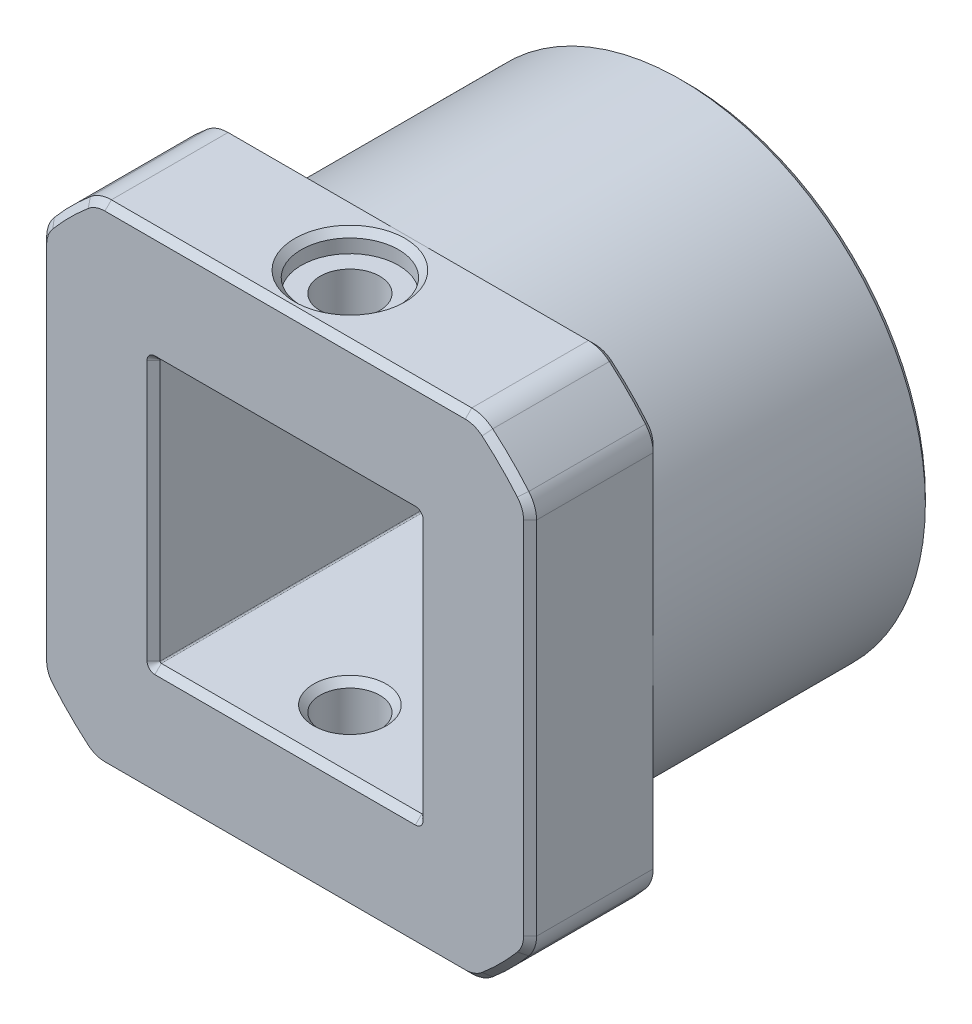
SolidWorks part; units mm, degrees
ref_plane "Front" through (0, 0, 0) normal (0, 0, 1) x (1, 0, 0)
ref_plane "Top" through (0, 0, 0) normal (0, 1, 0) x (1, 0, 0)
ref_plane "Right" through (0, 0, 0) normal (1, 0, 0) x (0, 0, -1)
sketch "Skizze1" plane through (0, 0, 0) normal (0, 0, 1) x (1, 0, 0)
  line L1 (-10.15, -10.15) -> (10.15, -10.15)
  line L2 (-10.15, -10.15) -> (-10.15, 10.15)
  line L3 (-10.15, 10.15) -> (10.15, 10.15)
  line L4 (10.15, -10.15) -> (10.15, 10.15)
  line L5 (-10.15, -10.15) -> (10.15, 10.15) construction
  line L6 (-10.15, 10.15) -> (10.15, -10.15) construction
  circle A0 centre (0, 0) radius 18.9
  point P0 (0, 0)
  dimension "D2" = 37.8
  dimension "D1" = 20.3
extrude "Aufsatz-Linear austragen1" add sketch "Skizze1" along normal blind 21
sketch "Skizze2" plane through (0, 0, 21) normal (0, 0, 1) x (1, 0, 0)
  line L0 (-14.7916, 18.9) -> (14.7916, 18.9)
  line L1 (-10.15, -10.15) -> (10.15, -10.15)
  line L2 (-10.15, -10.15) -> (-10.15, 10.15)
  line L3 (-10.15, 10.15) -> (10.15, 10.15)
  line L4 (10.15, -10.15) -> (10.15, 10.15)
  line L5 (-10.15, -10.15) -> (10.15, 10.15) construction
  line L6 (-10.15, 10.15) -> (10.15, -10.15) construction
  line L7 (0, 0) -> (13.8508, 0) construction
  line L8 (0, 0) -> (0, 13.2524) construction
  line L9 (18.9, -14.7916) -> (18.9, 14.7916)
  line L10 (14.7916, -18.9) -> (-14.7916, -18.9)
  line L11 (-18.9, 14.7916) -> (-18.9, -14.7916)
  arc A0 (-14.7916, 18.9) -> (-18.9, 14.7916) centre (0, 0) ccw
  circle A1 centre (0, 0) radius 18.9 construction
  arc A2 (-18.9, -14.7916) -> (-14.7916, -18.9) centre (0, 0) ccw
  arc A3 (14.7916, -18.9) -> (18.9, -14.7916) centre (0, 0) ccw
  arc A4 (18.9, 14.7916) -> (14.7916, 18.9) centre (0, 0) ccw
  point P1 (19.122, 11.8574)
  dimension "D1" = 48
extrude "Aufsatz-Linear austragen2" add sketch "Skizze2" along normal blind 10
sketch "Skizze3" plane through (0, 18.9, 0) normal (0, 1, 0) x (1, 0, 0)
  line L0 (0, -21) -> (0, -31) construction
  line L2 (14.7916, -31) -> (-14.7916, -31) construction
  circle A0 centre (0, -26) radius 2.3
  dimension "D1" = 4.6
  dimension "D2" = 10
extrude "Schnitt-Linear austragen1" cut sketch "Skizze3" against normal through all
pattern_circular "Kreismuster1" [suppressed] count 2 over 90 reverse direction yes of bodies 103
sketch "Sketch1" plane through (0, 18.9, 0) normal (0, 1, 0) x (1, 0, 0)
  circle A0 centre (0, -26) radius 3.75
  dimension "D1" = 7.5
extrude "Cut-Extrude1" cut sketch "Sketch1" against normal offset from surface (1.55 mm away) 7.2 up to face at (0, 10.15, 23.7)
extrude "Cut-Extrude2" cut sketch "Sketch1<2>" along normal offset from surface (1.55 mm away) 7.2 from surface up to face at (0, -10.15, 28.3) starting at face at (0, -18.9, 28.3)
sketch "Sketch1<2>" plane through (0, 18.9, 0) normal (0, 1, 0) x (1, 0, 0) same geometry as "Sketch1"
fillet "Verrundung1" radius 0.1 4 edges at (10.15, -10.15, 15.5) (-10.15, -10.15, 15.5) (-10.15, 10.15, 15.5) (10.15, 10.15, 15.5)
fillet "Verrundung2" radius 2.5 8 edges at (-18.9, -14.7916, 26) (-14.7916, -18.9, 26) (14.7916, -18.9, 26) (18.9, -14.7916, 26) (18.9, 14.7916, 26) (14.7916, 18.9, 26) (-18.9, 14.7916, 26) (-14.7916, 18.9, 26)
chamfer "Fase1" distance 0.5 angle 45 37 edges at (-10.1207, -10.1207, 0) (-10.15, 0, 0) (-10.1207, 10.1207, 0) (0, 10.15, 0) (10.1207, 10.1207, 0) (10.15, 0, 0) (10.1207, -10.1207, 0) (0, -10.15, 0) (18.9, 0, 0) (-10.1207, 10.1207, 31) (-10.15, 0, 31) (-10.1207, -10.1207, 31) (0, -10.15, 31) (10.1207, -10.1207, 31) (10.15, 0, 31) (10.1207, 10.1207, 31) (0, 10.15, 31) (-18.7471, 14.7639, 31) (-16.9706, 16.9706, 31) (-14.7639, 18.7471, 31) (0, 18.9, 31) (14.7639, 18.7471, 31) (16.9706, 16.9706, 31) (18.7471, 14.7639, 31) (18.9, 0, 31) (18.7471, -14.7639, 31) (16.9706, -16.9706, 31) (14.7639, -18.7471, 31) (0, -18.9, 31) (-14.7639, -18.7471, 31) (-16.9706, -16.9706, 31) (-18.7471, -14.7639, 31) (-18.9, 0, 31) (0, -10.15, 28.3) (0, 10.15, 23.7) (0, -18.9, 29.75) (0, 18.9, 29.75)
chamfer "Fase2" [suppressed] distance 0.3 angle 45
chamfer "Fase3" [suppressed] distance 0.5 angle 45
chamfer "Fase4" distance 0.5 angle 45 9 edges at (18.7471, 14.7639, 21) (-18.7471, 14.7639, 21) (16.9706, 16.9706, 21) (-16.9706, 16.9706, 21) (14.7639, 18.7471, 21) (-14.7639, 18.7471, 21) (6.9514, 18.9, 21) (-6.9514, 18.9, 21) (18.9, 6.9514, 21)
